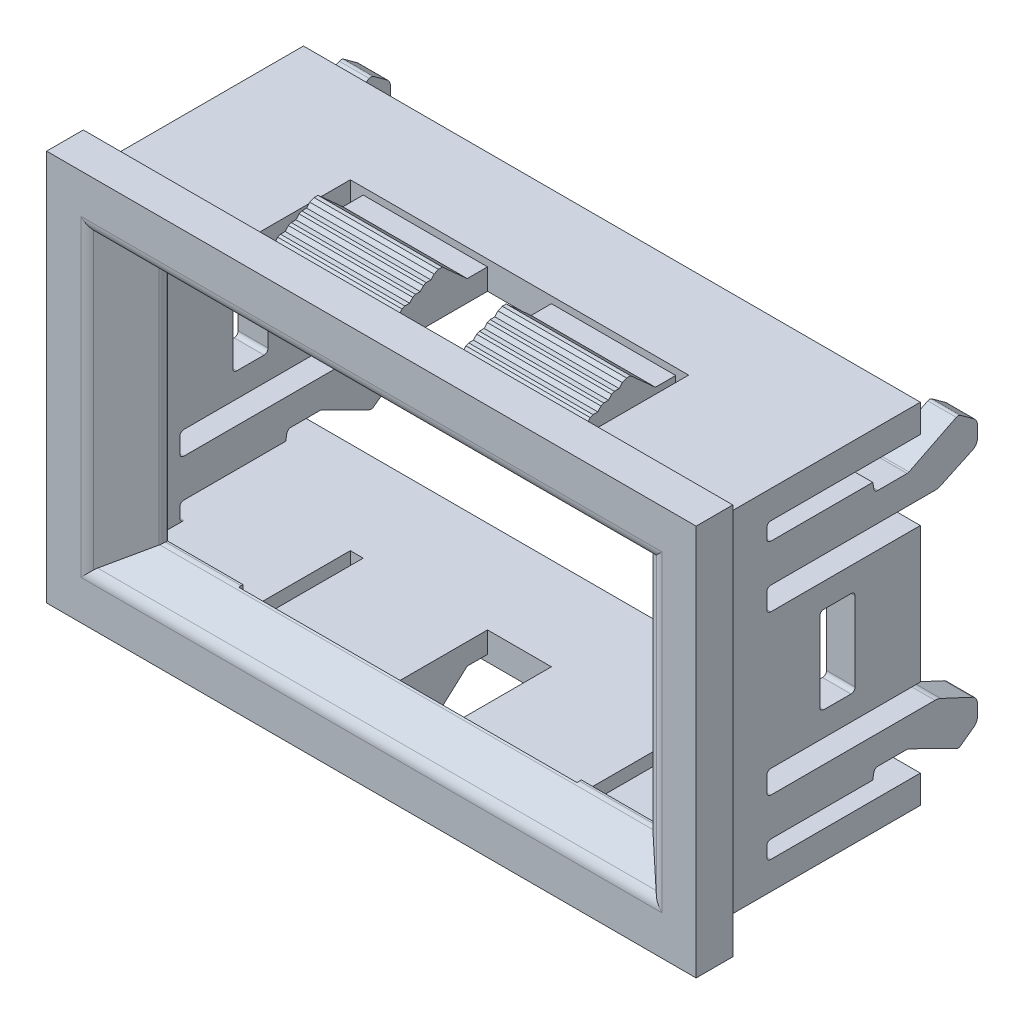
SolidWorks part; units mm, degrees
material "ABS"
ref_plane "Plan de face" through (0, 0, 0) normal (0, 0, 1) x (1, 0, 0)
ref_plane "Plan de dessus" through (0, 0, 0) normal (0, 1, 0) x (1, 0, 0)
ref_plane "Plan de droite" through (0, 0, 0) normal (1, 0, 0) x (0, 0, -1)
sketch "Esquisse1" plane through (0, 0, 0) normal (0, 0, 1) x (1, 0, 0)
  line L0 (0, 14.4) -> (0, -14.4) construction
  line L1 (-23.9, 14.4) -> (23.9, 14.4)
  line L2 (-23.9, 14.4) -> (-23.9, -14.4)
  line L3 (-23.9, -14.4) -> (23.9, -14.4)
  line L4 (23.9, 14.4) -> (23.9, -14.4)
  line L5 (-18, 0) -> (18, 0) construction
  line L6 (-18, 9) -> (18, 9) construction
  line L7 (-18, 9) -> (-18, -9) construction
  line L8 (-18, -9) -> (18, -9) construction
  line L9 (18, 9) -> (18, -9) construction
  line L11 (21, 11) -> (-21, 11) construction
  line L12 (21, 11) -> (21, -11) construction
  line L13 (21, -11) -> (-21, -11) construction
  line L14 (-21, 11) -> (-21, -11) construction
  line L15 (21, 11) -> (-21, -11) construction
  line L16 (21, -11) -> (-21, 11) construction
  point P13 (0, 0)
  dimension "D1" = 47.8
  dimension "D2" = 28.8
  dimension "D3" = 36
  dimension "D4" = 18
  dimension "D5" = 42
  dimension "D6" = 22
extrude "Boss.-Extru.1" add sketch "Esquisse1" along normal blind 2.7
sketch "Esquisse2" plane through (0, 0, 0) normal (0, 0, -1) x (-1, 0, 0)
  line L0 (-22.7, 12.85) -> (22.7, -12.85) construction
  line L1 (-22.7, 12.85) -> (22.7, 12.85)
  line L2 (-22.7, 12.85) -> (-22.7, -12.85)
  line L3 (-22.7, -12.85) -> (22.7, -12.85)
  line L4 (22.7, 12.85) -> (22.7, -12.85)
  dimension "D1" = 45.4
  dimension "D2" = 25.7
extrude "Boss.-Extru.2" add sketch "Esquisse2" along normal blind 19.2
sketch "Esquisse3" plane through (0, 0, 2.7) normal (0, 0, 1) x (1, 0, 0)
  line L4 (21, 11) -> (-21, 11) construction
  line L5 (-21, 11) -> (-21, -11) construction
  line L6 (21, -11) -> (-21, -11) construction
  line L7 (21, 11) -> (21, -11) construction
  line L8 (21, 11) -> (-21, 11)
  line L9 (-21, 11) -> (-21, -11)
  line L10 (21, -11) -> (-21, -11)
  line L11 (21, 11) -> (21, -11)
extrude "Enlèv. mat.-Extru.1" cut sketch "Esquisse3" against normal blind 3
sketch "Esquisse5" plane through (0, 0, 0) normal (1, 0, 0) x (0, 0, -1)
  line L0 (-2.7, 11) -> (0, 9)
  line L1 (0.3, 9) -> (0, 9)
  line L2 (0.3, 9) -> (0.3, 11)
  line L3 (0.3, 11) -> (-2.7, 11)
  line L4 (0.3, -11) -> (-2.7, -11)
  line L5 (0.3, 11) -> (0.3, -11) construction
  line L6 (-12.5772, 0) -> (0, 0) construction
  line L7 (0.3, -9) -> (0.3, -11)
  line L8 (0.3, -9) -> (0, -9)
  line L9 (-2.7, -11) -> (0, -9)
  point P10 (-13.8367, -15.9553)
  dimension "D1" = 0.3
extrude "Boss.-Extru.3" add sketch "Esquisse5" along normal up to next and the other way up to next
sketch "Esquisse6" plane through (0, 0, 0) normal (0, 1, 0) x (1, 0, 0)
  line L0 (-21, -2.7) -> (-18, 0)
  line L1 (0, 0) -> (0, -2.3866) construction
  line L2 (-21, -2.7) -> (-21, 0.3)
  line L3 (-21, 0.3) -> (-18, 0.3)
  line L4 (-18, 0) -> (-18, 0.3)
  line L5 (-21, 0.3) -> (21, 0.3) construction
  line L6 (-21, 0) -> (21, 0) construction
  line L7 (18, 0) -> (18, 0.3)
  line L8 (21, 0.3) -> (18, 0.3)
  line L9 (21, -2.7) -> (21, 0.3)
  line L10 (21, -2.7) -> (18, 0)
extrude "Boss.-Extru.4" add sketch "Esquisse6" along normal up to next and the other way up to next
fillet "Congé1" radius 0.5 4 edges at (0, -9, 0) (18, 0, 0) (-18, 0, 0) (0, 9, 0)
fillet "Congé2" radius 1 4 edges at (0, 11, 2.7) (-21, 0, 2.7) (21, 0, 2.7) (0, -11, 2.7)
sketch "Esquisse7" plane through (0, 0, -19.2) normal (0, 0, -1) x (-1, 0, 0)
  line L0 (20.5, 0) -> (0, 0) construction
  line L1 (-20.6, 10.79) -> (20.5, 10.79)
  line L2 (-20.6, 10.79) -> (-20.6, -10.79)
  line L3 (-20.6, -10.79) -> (20.5, -10.79)
  line L4 (20.5, 10.79) -> (20.5, -10.79)
  line L5 (22.7, 12.85) -> (-22.7, 12.85) construction
  line L6 (22.7, -12.85) -> (22.7, 12.85) construction
  line L7 (-22.7, 12.85) -> (-22.7, -12.85) construction
  dimension "D1" = 2.06
  dimension "D2" = 2.2
  dimension "D3" = 2.1
extrude "Enlèv. mat.-Extru.2" cut sketch "Esquisse7" against normal up to surface (18.9 mm away) up to face at (0, 0, -0.3)
sketch "Esquisse9" plane through (0, 0, 0) normal (1, 0, 0) x (0, 0, -1)
  line L0 (-16.4519, 0) -> (22.2431, 0) construction
  line L1 (7.9, 3.2) -> (9.9, 3.2)
  line L2 (7.6, 2.9) -> (7.6, -2.9)
  line L3 (7.9, -3.2) -> (9.9, -3.2)
  line L4 (10.2, 2.9) -> (10.2, -2.9)
  line L5 (26.29, 0) -> (-26.29, 0) construction
  line L6 (0.3, 10.79) -> (19.2, 10.79) construction
  line L7 (4, 10.79) -> (15, 10.79)
  line L8 (3.7, 10.49) -> (3.7, 9.79)
  line L9 (4, 4.99) -> (15, 4.99)
  line L10 (15, 10.79) -> (15, 12.85)
  line L11 (0, 21.9617) -> (0, -21.9617) construction
  line L12 (3.7, 6.39) -> (3.7, 5.29)
  line L13 (4, 9.49) -> (11.5, 9.49)
  line L14 (11.5, 9.49) -> (11.5797, 9.0379)
  line L15 (4, 6.69) -> (16.0783, 6.69)
  line L16 (11.8752, 8.79) -> (14.0294, 8.79)
  line L17 (17.647, 10.5585) -> (14.1632, 8.8215)
  line L18 (16.5009, 6.7837) -> (18.8536, 7.8807)
  line L19 (17.9572, 10.5327) -> (18.9527, 9.8095)
  line L20 (19.2, 8.4245) -> (19.2, 9.3241)
  line L21 (19.2, 12.85) -> (19.2, -12.85) construction
  line L22 (15, 12.85) -> (22.2431, 12.85)
  line L23 (19.2, 12.85) -> (0, 12.85) construction
  line L24 (19.2, -8.4245) -> (19.2, -9.3241)
  line L25 (15, 4.99) -> (15, -4.99)
  line L26 (22.2431, 12.85) -> (22.2431, -12.85)
  line L27 (17.9572, -10.5327) -> (18.9527, -9.8095)
  line L28 (16.5009, -6.7837) -> (18.8536, -7.8807)
  line L29 (17.647, -10.5585) -> (14.1632, -8.8215)
  line L30 (11.8752, -8.79) -> (14.0294, -8.79)
  line L31 (4, -6.69) -> (16.0783, -6.69)
  line L32 (11.5, -9.49) -> (11.5797, -9.0379)
  line L33 (4, -9.49) -> (11.5, -9.49)
  line L34 (3.7, -6.39) -> (3.7, -5.29)
  line L35 (15, -10.79) -> (15, -12.85)
  line L36 (4, -4.99) -> (15, -4.99)
  line L37 (3.7, -10.49) -> (3.7, -9.79)
  line L38 (4, -10.79) -> (15, -10.79)
  line L39 (15, -12.85) -> (22.2431, -12.85)
  arc A0 (17.647, 10.5585) -> (17.9572, 10.5327) centre (17.7809, 10.29) cw
  arc A1 (3.7, 10.49) -> (4, 10.79) centre (4, 10.49) cw
  arc A2 (3.7, 9.79) -> (4, 9.49) centre (4, 9.79) ccw
  arc A3 (3.7, 5.29) -> (4, 4.99) centre (4, 5.29) ccw
  arc A4 (3.7, 6.39) -> (4, 6.69) centre (4, 6.39) cw
  arc A5 (14.1632, 8.8215) -> (14.0294, 8.79) centre (14.0294, 9.09) cw
  arc A6 (11.5797, 9.0379) -> (11.8752, 8.79) centre (11.8752, 9.09) ccw
  arc A7 (16.5009, 6.7837) -> (16.0783, 6.69) centre (16.0783, 7.69) cw
  arc A8 (19.2, 9.3241) -> (18.9527, 9.8095) centre (18.6, 9.3241) ccw
  arc A9 (18.8536, 7.8807) -> (19.2, 8.4245) centre (18.6, 8.4245) ccw
  arc A10 (9.9, 3.2) -> (10.2, 2.9) centre (9.9, 2.9) cw
  arc A11 (10.2, -2.9) -> (9.9, -3.2) centre (9.9, -2.9) cw
  arc A12 (7.9, -3.2) -> (7.6, -2.9) centre (7.9, -2.9) cw
  arc A13 (7.6, 2.9) -> (7.9, 3.2) centre (7.9, 2.9) cw
  arc A14 (18.8536, -7.8807) -> (19.2, -8.4245) centre (18.6, -8.4245) cw
  arc A15 (19.2, -9.3241) -> (18.9527, -9.8095) centre (18.6, -9.3241) cw
  arc A16 (16.5009, -6.7837) -> (16.0783, -6.69) centre (16.0783, -7.69) ccw
  arc A17 (11.5797, -9.0379) -> (11.8752, -8.79) centre (11.8752, -9.09) cw
  arc A18 (14.1632, -8.8215) -> (14.0294, -8.79) centre (14.0294, -9.09) ccw
  arc A19 (3.7, -6.39) -> (4, -6.69) centre (4, -6.39) ccw
  arc A20 (3.7, -5.29) -> (4, -4.99) centre (4, -5.29) cw
  arc A21 (3.7, -9.79) -> (4, -9.49) centre (4, -9.79) cw
  arc A22 (3.7, -10.49) -> (4, -10.79) centre (4, -10.49) ccw
  arc A23 (17.647, -10.5585) -> (17.9572, -10.5327) centre (17.7809, -10.29) ccw
  point P35 (3.7, 10.79)
  point P38 (3.7, 9.49)
  point P45 (14.1, 8.79)
  point P50 (16.3, 6.69)
  point P65 (7.6, -3.2)
  point P68 (7.6, 3.2)
  dimension "D18" = 0.3
  dimension "D19" = 0.3
  dimension "D20" = 0.3
  dimension "D21" = 1
  dimension "D22" = 0.6
  dimension "D23" = 0.3
  dimension "D1" = 15
  dimension "D2" = 3.7
  dimension "D3" = 2.8
  dimension "D4" = 1.7
  dimension "D5" = 1.3
  dimension "D6" = 6.4
  dimension "D7" = 7.6
  dimension "D8" = 2.6
  dimension "D9" = 7.8
  dimension "D10" = 2.1
  dimension "D11" = 10
  dimension "D12" = 25
  dimension "D13" = 2.9
  dimension "D14" = 5.1
  dimension "D15" = 26.5
  dimension "D16" = 0.2
  dimension "D17" = 54
extrude "Enlèv. mat.-Extru.3" cut sketch "Esquisse9" against normal through all and the other way through all
sketch "Esquisse12" plane through (0, 0, 0) normal (0, 1, 0) x (1, 0, 0)
  line L0 (0, 16.5317) -> (0, -8.5013) construction
  line L1 (-12.45, 8.2) -> (-11.5, 8.2)
  line L2 (-12.45, 8.2) -> (-12.45, 0)
  line L3 (-12.45, 0) -> (12.45, 0)
  line L4 (12.45, 8.2) -> (12.45, 0)
  line L5 (0, -15.2357) -> (0, 15.2357) construction
  line L6 (-15.84, 0) -> (15.84, 0) construction
  line L7 (-11.5, 8.2) -> (-11.5, 1.6)
  line L8 (-2.35, 8.2) -> (-2.35, 1.6)
  line L9 (-11.5, 1.6) -> (-2.35, 1.6)
  line L10 (2.35, 8.2) -> (2.35, 1.6)
  line L11 (11.5, 1.6) -> (2.35, 1.6)
  line L12 (11.5, 8.2) -> (11.5, 1.6)
  line L13 (-2.35, 8.2) -> (2.35, 8.2)
  line L14 (11.5, 8.2) -> (12.45, 8.2)
  dimension "D1" = 24.9
  dimension "D2" = 23
  dimension "D3" = 8.2
  dimension "D4" = 4.7
  dimension "D5" = 1.6
extrude "Enlèv. mat.-Extru.4" cut sketch "Esquisse12" against normal through all and the other way through all
sketch "Esquisse13" plane through (-2.35, 0, 0) normal (1, 0, 0) x (0, 0, -1)
  line L0 (4.7769, 14.0864) -> (6.15, 12.85)
  line L1 (2, 12.85) -> (4.7769, 14.0864)
  line L2 (2, 12.85) -> (6.15, 12.85)
  line L3 (15, 12.85) -> (0, 12.85) construction
  line L4 (0, 15.84) -> (0, -15.84) construction
  line L7 (-6.9745, 0) -> (4.1259, 0) construction
  line L8 (2, -12.85) -> (6.15, -12.85)
  line L9 (2, -12.85) -> (4.7769, -14.0864)
  line L10 (4.7769, -14.0864) -> (6.15, -12.85)
  dimension "D1" = 42
  dimension "D2" = 6.15
  dimension "D3" = 24
  dimension "D4" = 2
extrude "Boss.-Extru.5" add sketch "Esquisse13" against normal up to surface (9.15 mm away) up to face at (-11.5, 11.82, -4.9)
sketch "Esquisse14" plane through (2.35, 0, 0) normal (-1, 0, 0) x (0, 0, 1)
  line L3 (-2, -12.85) -> (-6.15, -12.85)
  line L4 (-6.15, -12.85) -> (-4.7769, -14.0864)
  line L5 (-4.7769, -14.0864) -> (-2, -12.85)
  line L6 (-2, -12.85) -> (-6.15, -12.85)
  line L7 (-6.15, -12.85) -> (-4.7769, -14.0864)
  line L8 (-4.7769, -14.0864) -> (-2, -12.85)
  line L9 (-4.7769, 14.0864) -> (-6.15, 12.85)
  line L10 (-6.15, 12.85) -> (-2, 12.85)
  line L11 (-2, 12.85) -> (-4.7769, 14.0864)
  line L12 (-4.7769, 14.0864) -> (-6.15, 12.85)
  line L13 (-6.15, 12.85) -> (-2, 12.85)
  line L14 (-2, 12.85) -> (-4.7769, 14.0864)
  dimension "D1" = 0
  dimension "D2" = 0
extrude "Boss.-Extru.6" add sketch "Esquisse14" against normal up to surface (9.15 mm away) up to face at (11.5, 11.82, -4.9)
sketch "Esquisse16" plane through (0, 0, 0) normal (1, 0, 0) x (0, 0, -1)
  line L0 (4.8728, 14) -> (6.7053, 12.35)
  line L1 (4.7769, 14.0864) -> (8.2, 14.0864)
  line L2 (8.2, 10.79) -> (8.2, 12.85) construction
  line L3 (6.7053, 12.35) -> (8.2, 12.35)
  line L4 (8.2, 14.0864) -> (8.2, 12.35)
  line L5 (4.7769, 14.0864) -> (6.15, 12.85) construction
  line L6 (6.15, 12.85) -> (8.2, 12.85) construction
  line L7 (1.7448, 0) -> (10.4387, 0) construction
  line L8 (1.6, 12.6719) -> (1.9104, 12.8101) construction
  line L9 (1.9104, 12.8101) -> (1.6, 12.4654)
  line L10 (1.9104, 12.8101) -> (2, 12.85)
  line L11 (2.1123, 12.9) -> (1.9104, 12.8101) construction
  line L12 (4.8728, 14) -> (4.5829, 14)
  line L13 (4.5829, 14) -> (4.7769, 14.0864)
  line L14 (4.7769, 14.0864) -> (2, 12.85) construction
  line L15 (4.0345, 13.6) -> (3.6845, 13.6)
  line L16 (4.0345, 13.6) -> (4.2687, 13.8601)
  line L17 (4.2687, 13.8601) -> (3.6845, 13.6)
  line L18 (3.4826, 13.5101) -> (2.8984, 13.25)
  line L19 (2.8984, 13.25) -> (3.2484, 13.25)
  line L20 (3.4826, 13.5101) -> (3.2484, 13.25)
  line L21 (2.6965, 13.1601) -> (2.1123, 12.9)
  line L22 (2.1123, 12.9) -> (2.4623, 12.9)
  line L23 (2.6965, 13.1601) -> (2.4623, 12.9)
  line L24 (3.6845, 13.6) -> (3.4826, 13.5101) construction
  line L25 (2.8984, 13.25) -> (2.6965, 13.1601) construction
  line L26 (1.6, 12.85) -> (2, 12.85)
  line L27 (2, 12.85) -> (1.6, 12.85) construction
  line L28 (1.6, 12.85) -> (1.6, 12.4654)
  line L29 (1.6, 10.79) -> (1.6, 12.85) construction
  dimension "D1" = 0.5
  dimension "D2" = 28
  dimension "D3" = 27.2
  dimension "D4" = 48
  dimension "D5" = 0.35
  dimension "D6" = 26.5
extrude "Enlèv. mat.-Extru.5" cut sketch "Esquisse16" against normal up to surface and the other way up to surface up to face at (-11.5, 12.4381, -4.6467) other way up to face at (11.5, 12.4381, -4.6467)
mirror "Symétrie1" about plane through (0, 0, 0) normal (0, 1, 0) of "Enlèv. mat.-Extru.5"
